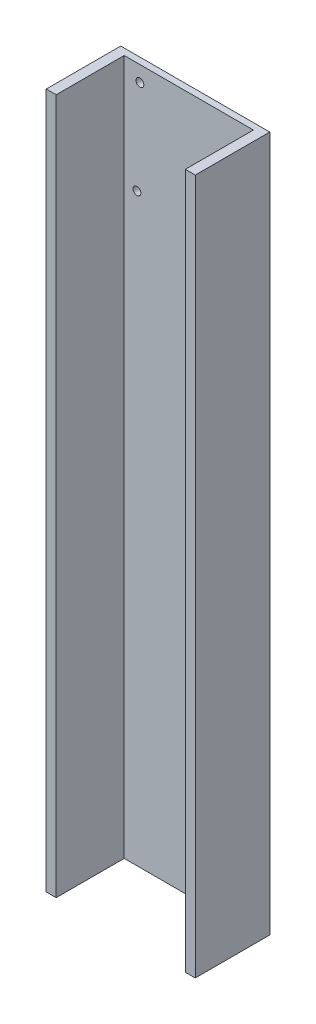
SolidWorks part; units mm, degrees
ref_plane "Front" through (0, 0, 0) normal (0, 0, 1) x (1, 0, 0)
ref_plane "Top" through (0, 0, 0) normal (0, 1, 0) x (1, 0, 0)
ref_plane "Right" through (0, 0, 0) normal (1, 0, 0) x (0, 0, -1)
sketch "Sketch1" plane through (0, 0, 0) normal (0, 1, 0) x (1, 0, 0)
  line L0 (-38.1, -19.05) -> (-33.02, -19.05)
  line L1 (-38.1, -19.05) -> (38.1, -19.05) construction
  line L2 (-38.1, -19.05) -> (-38.1, 19.05)
  line L3 (-38.1, 19.05) -> (38.1, 19.05)
  line L4 (38.1, -19.05) -> (38.1, 19.05)
  line L5 (-38.1, -19.05) -> (38.1, 19.05) construction
  line L6 (-38.1, 19.05) -> (38.1, -19.05) construction
  line L7 (-33.02, -19.05) -> (-33.02, 15.748)
  line L8 (-33.02, 15.748) -> (33.02, 15.748)
  line L9 (33.02, 15.748) -> (33.02, -19.05)
  line L10 (33.02, -19.05) -> (38.1, -19.05)
  point P0 (0, 0)
  dimension "D1" = 76.2
  dimension "D2" = 38.1
  dimension "D3" = 3.302
  dimension "D4" = 5.08
extrude "Boss-Extrude1" add sketch "Sketch1" along normal mid plane 355.6
sketch "Sketch2" plane through (0, 0, -15.748) normal (0, 0, 1) x (1, 0, 0)
  line L0 (-33.02, 177.8) -> (-33.02, -177.8) construction
  line L1 (-33.02, 177.8) -> (-25.02, 177.8) construction
  line L2 (-33.02, 177.8) -> (-33.02, 169.8) construction
  line L3 (-33.02, 169.8) -> (-25.02, 169.8) construction
  line L4 (-25.02, 177.8) -> (-25.02, 169.8) construction
  circle A0 centre (-25.02, 169.8) radius 2
  circle A1 centre (-26.52, 121.0335) radius 2
  circle A2 centre (-7.22, 127.3835) radius 1.5 construction
  arc A3 (-7.22, 127.3835) -> (-20.17, 101.7335) centre (-26.52, 121.0335) cw construction
  arc A4 (-19.7012, 100.3086) -> (-5.7951, 127.8523) centre (-26.52, 121.0335) ccw construction
  arc A5 (-20.6388, 103.1584) -> (-8.6449, 126.9147) centre (-26.52, 121.0335) ccw construction
  arc A6 (-20.6388, 103.1584) -> (-19.7012, 100.3086) centre (-20.17, 101.7335) ccw construction
  arc A7 (-5.7951, 127.8523) -> (-8.6449, 126.9147) centre (-7.22, 127.3835) ccw construction
  point P10 (-8.3827, 111.8765)
  point P18 (0, 0)
  dimension "D2" = 4
  dimension "D7" = 4
  dimension "D8" = 3
  dimension "D1" = 8
  dimension "D3" = 19.3
  dimension "D4" = 6.35
  dimension "D5" = 6.5
  dimension "D6" = 46
  dimension "D9" = 90
extrude "Cut-Extrude1" cut sketch "Sketch2" against normal through all
